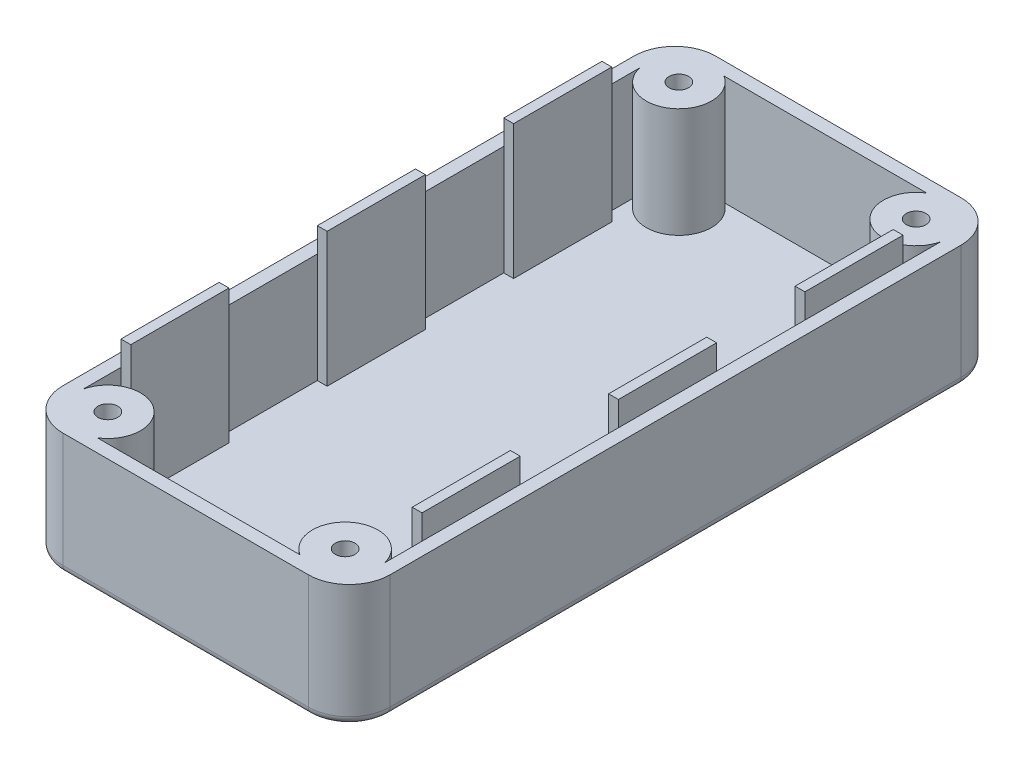
SolidWorks part; units mm, degrees
ref_plane "Front Plane" through (0, 0, 0) normal (0, 0, 1) x (1, 0, 0)
ref_plane "Top Plane" through (0, 0, 0) normal (0, 1, 0) x (1, 0, 0)
ref_plane "Right Plane" through (0, 0, 0) normal (1, 0, 0) x (0, 0, -1)
sketch "Base Sketch" plane through (0, 0, 0) normal (0, 1, 0) x (1, 0, 0)
  line L1 (0, 0) -> (40, 0)
  line L2 (0, 0) -> (0, 79.79)
  line L3 (0, 79.79) -> (40, 79.79)
  line L4 (40, 0) -> (40, 79.79)
extrude "Base" add sketch "Base Sketch" along normal blind 15
fillet "Corner Rounds R5" radius 5 4 edges at (0, 7.5, -79.79) (40, 7.5, -79.79) (40, 7.5, 0) (0, 7.5, 0)
shell "Shell" thickness 1.6 removed face at (20, 15, -39.895)
sketch "Sketch2" plane through (0, 0, 0) normal (0, 1, 0) x (1, 0, 0)
  circle A0 centre (5.5, 5) radius 4
  circle A1 centre (34.5, 5) radius 4
  circle A2 centre (5.5, 74.79) radius 4
  circle A3 centre (34.5, 74.79) radius 4
extrude "Screw Bosses" add sketch "Sketch2" along normal blind 15
sketch "Sketch3" plane through (0, 0, 0) normal (0, 1, 0) x (1, 0, 0)
  line L1 (1.6, 10.5) -> (2.8, 10.5)
  line L2 (1.6, 10.5) -> (1.6, 22.5)
  line L3 (1.6, 22.5) -> (2.8, 22.5)
  line L4 (2.8, 10.5) -> (2.8, 22.5)
  line L6 (1.6, 34.5) -> (2.8, 34.5)
  line L7 (1.6, 34.5) -> (1.6, 46.5)
  line L8 (1.6, 46.5) -> (2.8, 46.5)
  line L9 (2.8, 34.5) -> (2.8, 46.5)
  line L11 (1.6, 57.29) -> (2.8, 57.29)
  line L12 (1.6, 57.29) -> (1.6, 69.29)
  line L13 (1.6, 69.29) -> (2.8, 69.29)
  line L14 (2.8, 57.29) -> (2.8, 69.29)
  line L16 (37.2, 10.5) -> (38.4, 10.5)
  line L17 (37.2, 10.5) -> (37.2, 22.5)
  line L18 (37.2, 22.5) -> (38.4, 22.5)
  line L19 (38.4, 10.5) -> (38.4, 22.5)
  line L21 (37.2, 34.5) -> (38.4, 34.5)
  line L22 (37.2, 34.5) -> (37.2, 46.5)
  line L23 (37.2, 46.5) -> (38.4, 46.5)
  line L24 (38.4, 34.5) -> (38.4, 46.5)
  line L26 (37.2, 57.29) -> (38.4, 57.29)
  line L27 (37.2, 57.29) -> (37.2, 69.29)
  line L28 (37.2, 69.29) -> (38.4, 69.29)
  line L29 (38.4, 57.29) -> (38.4, 69.29)
extrude "Alignment Tabs" add sketch "Sketch3" along normal blind 18
fillet "Bottom Edge Round R1" radius 1 8 edges at (1.4645, 0, -1.4645) (20, 0, 0) (38.5355, 0, -1.4645) (40, 0, -39.895) (38.5355, 0, -78.3255) (20, 0, -79.79) (1.4645, 0, -78.3255) (0, 0, -39.895)
sketch "Sketch4" plane through (0, 0, 0) normal (0, 1, 0) x (1, 0, 0)
  circle A0 centre (5.5, 5) radius 1.2
  circle A1 centre (34.5, 5) radius 1.2
  circle A2 centre (5.5, 74.79) radius 1.2
  circle A3 centre (34.5, 74.79) radius 1.2
extrude "M2 Clearance Holes" cut sketch "Sketch4" along normal through all
sketch "Sketch5" plane through (0, 0, 0) normal (0, 1, 0) x (1, 0, 0)
  circle A0 centre (5.5, 5) radius 2.2
  circle A1 centre (34.5, 5) radius 2.2
  circle A2 centre (5.5, 74.79) radius 2.2
  circle A3 centre (34.5, 74.79) radius 2.2
extrude "M2 Counterbores" cut sketch "Sketch5" along normal blind 11
